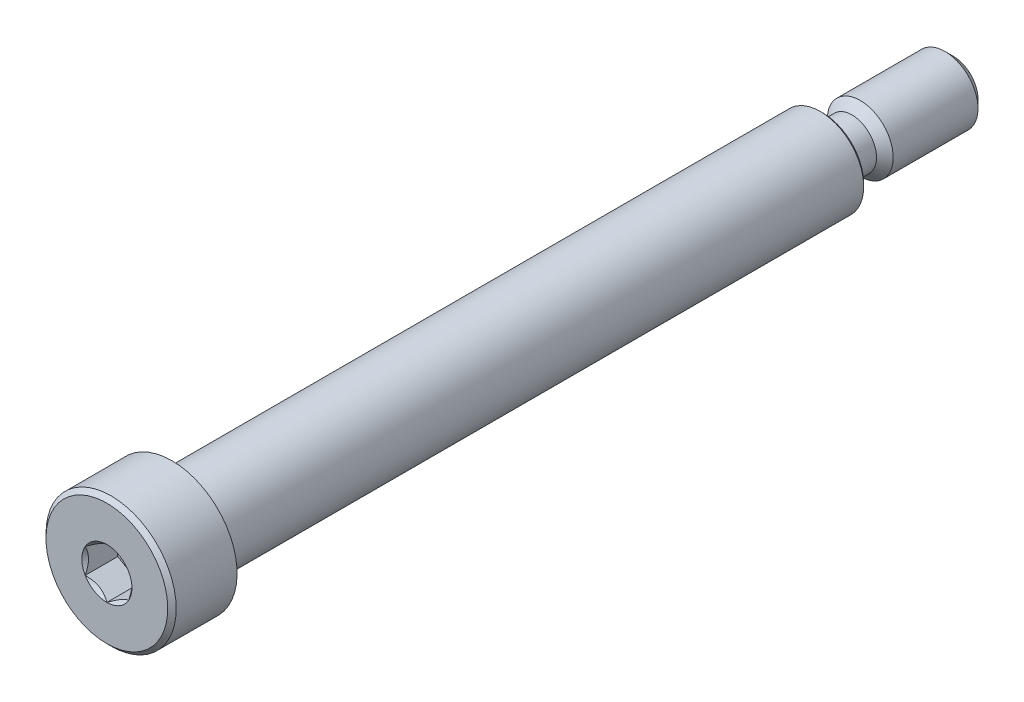
SolidWorks part; units mm, degrees
ref_plane "Front" through (0, 0, 0) normal (0, 0, 1) x (1, 0, 0)
ref_plane "Top" through (0, 0, 0) normal (0, 1, 0) x (1, 0, 0)
ref_plane "Right" through (0, 0, 0) normal (1, 0, 0) x (0, 0, -1)
sketch "Sketch1" plane through (0, 0, 0) normal (1, 0, 0) x (0, 0, -1)
  line L0 (0, 4.7625) -> (4.7625, 4.7625)
  line L1 (4.7625, 4.7625) -> (4.7625, 3.175)
  line L2 (4.7625, 3.175) -> (52.3875, 3.175)
  line L3 (52.3875, 3.175) -> (52.3875, 2.413)
  line L4 (52.3875, 2.413) -> (61.9125, 2.413)
  line L5 (61.9125, 2.413) -> (61.9125, 0)
  line L6 (61.9125, 0) -> (0, 0)
  line L7 (0, 0) -> (0, 4.7625)
  line L8 (0, 4.7625) -> (0, -4.7625) construction
  line L9 (61.9125, 2.413) -> (61.9125, -2.413) construction
  line L10 (52.3875, 3.175) -> (52.3875, -3.175) construction
  line L11 (61.9125, -2.413) -> (60.2347, -2.413) construction
  line L12 (28.575, 0) -> (28.575, 3.175) construction
  point P8 (60.325, -2.413)
  point P12 (52.3875, 0)
  point P17 (9.525, 3.175)
  point P18 (28.575, 0)
  point P19 (28.575, 3.175)
  point P20 (47.625, 3.175)
  point P21 (47.625, -3.175)
  point P22 (9.525, -3.175)
  dimension "Head Dia" = 9.525
  dimension "Head Ht" = 4.7625
  dimension "Thread Lg" = 9.525
  dimension "Thread Dia" = 4.826
  dimension "Shoulder Dia" = 6.35
  dimension "Shoulder Lg" = 47.625
  dimension "D1" = 1.5875
  dimension "D2" = 1.6778
  dimension "D3" = 23.8125
  dimension "D4" = 4.7625
revolve "Revolve1" add sketch "Sketch1" angle 360 mid plane about L6
ref_plane "Plane1" through (0, 0, -61.9125) normal (0, 0, 1) x (1, 0, 0)
sketch "Sketch3" [suppressed] plane through (0, 0, -61.9125) normal (0, 0, 1) x (1, 0, 0)
  circle A0 centre (0, 0) radius 2.413
sketch "Sketch5" plane through (0, 0, 0) normal (1, 0, 0) x (0, 0, -1)
  line L0 (52.3875, 3.175) -> (55.8673, 3.175)
  line L1 (55.8673, 3.175) -> (54.4957, 1.8034)
  line L2 (54.4957, 1.8034) -> (52.9971, 1.8034)
  line L3 (52.3875, 3.175) -> (52.3875, 2.413)
  line L5 (52.3875, 2.413) -> (61.9125, 2.413) construction
  line L6 (61.9125, 0) -> (54.4957, 0) construction
  line L7 (58.2041, 0) -> (58.2041, -2.413) construction
  arc A0 (52.3875, 2.413) -> (52.9971, 1.8034) centre (52.9971, 2.413) ccw
  dimension "D1" = 45
  dimension "CADB" = 2.1082
  dimension "CADA" = 3.6068
revolve "Cut-Revolve1" cut sketch "Sketch5" angle 360 mid plane about L6
chamfer "Chamfer1" distance 0.6032 angle 45 1 edges at (0, 2.413, -61.9125)
chamfer "Chamfer2" distance 0.3096 angle 45 1 edges at (0, 4.7625, 0)
chamfer "Chamfer3" distance 0.2032 angle 45 1 edges at (0, 3.175, -52.3875)
sketch "Sketch10" plane through (0, 0, 0) normal (1, 0, 0) x (0, 0, -1)
  line L0 (0.3096, 0) -> (4.4529, 0) construction
  line L1 (0.3096, -4.7625) -> (0.3096, 4.7625) construction
  line L3 (0.3096, 0) -> (0, 0) construction
  line L4 (4.4529, 0) -> (4.7625, 0) construction
  line L5 (4.7625, -4.7625) -> (4.7625, 4.7625) construction
  point P6 (2.3812, 0)
  dimension "D1" = 4.1434
ref_plane "Plane2" through (0, 0, -2.3812) normal (0, 0, 1) x (1, 0, 0)
sketch "Sketch11" plane through (0, 0, -2.3812) normal (0, 0, 1) x (1, 0, 0)
  line L0 (0, 4.5148) -> (0, 4.7625) construction
  line L1 (0, 4.5148) -> (0.143, 4.7625)
  line L2 (0, 4.5148) -> (-0.143, 4.7625)
  line L3 (-0.143, 4.7625) -> (0.143, 4.7625)
  line L4 (0, 0) -> (-0.143, 4.7625) construction
  line L5 (0.143, 4.7625) -> (0, 0) construction
  circle A1 centre (0, 0) radius 4.7625 construction
  circle A2 centre (0, 0) radius 4.5148 construction
  circle A3 centre (0, 0) radius 4.4529 construction
  point P3 (0, 0.0018)
  point P8 (2.3908, 0.7309)
  dimension "D1" = 0.2476
  dimension "D2" = 3.439
extrude "Cut-Extrude5" [suppressed] cut sketch "Sketch11" against normal mid plane 3.9362
pattern_circular "CirPattern1" [suppressed] count 99 over 360 of bodies 119
sketch "Sketch8" plane through (0, 0, 0) normal (0, 0, 1) x (1, 0, 0)
  line L1 (1.5875, 0.9165) -> (0, 1.8331)
  line L2 (0, 1.8331) -> (-1.5875, 0.9165)
  line L3 (-1.5875, 0.9165) -> (-1.5875, -0.9165)
  line L4 (-1.5875, -0.9165) -> (0, -1.8331)
  line L5 (0, -1.8331) -> (1.5875, -0.9165)
  line L6 (1.5875, -0.9165) -> (1.5875, 0.9165)
  circle A0 centre (0, 0) radius 1.5875 construction
  dimension "Hex" = 3.175
extrude "Cut-Extrude2" cut sketch "Sketch8" against normal blind 2.3813
sketch "Sketch9" plane through (0, 0, 0) normal (0, 0, 1) x (1, 0, 0)
  circle A0 centre (0, 0) radius 1.8331
extrude "Cut-Extrude4" cut sketch "Sketch9" against normal blind 2.3813 draft 45
sketch "Front Sketch" plane through (0, 0, 0) normal (0, 0, 1) x (1, 0, 0)
  line L0 (1.5875, -0.9165) -> (1.5875, 0.9165) construction
  line L1 (-1.5875, 0.9165) -> (-1.5875, -0.9165) construction
  circle A0 centre (0, 0) radius 4.7625 construction
  point P4 (-1.5875, 0)
  point P5 (1.5875, 0)
  point P6 (4.7625, 0)
  point P9 (-4.7625, 0)
ref_plane "Contact Plane 1" through (0, 0, -4.7625) normal (0, 0, -1) x (-1, 0, 0)
ref_axis "Center Axis 1" through (0, 0, -61.9125) along (0, 0, 1)
curve "Helix/Spiral1" [suppressed] pitch 1.0583 height 10.5833 turns 10
sketch "Sketch4" [suppressed] plane through (0, 0, 0) normal (1, 0, 0) x (0, 0, -1)
  line L0 (61.8464, 2.5276) -> (62.9047, 2.5276) construction
  line L1 (62.9047, 2.5276) -> (62.3755, 1.611) construction
  line L3 (62.3755, 1.611) -> (61.8464, 2.5276) construction
  line L4 (61.8794, 2.4703) -> (62.8716, 2.4703) construction
  line L5 (61.9125, 2.413) -> (62.8385, 2.413) construction
  line L6 (62.3094, 1.7256) -> (62.4417, 1.7256) construction
  line L7 (62.3755, 1.7256) -> (62.3755, 1.611) construction
  line L8 (62.3755, 2.5276) -> (62.3755, 2.413) construction
  line L9 (61.8794, 2.4703) -> (62.8716, 2.4703)
  line L10 (62.8716, 2.4703) -> (62.4417, 1.7256)
  line L11 (62.4417, 1.7256) -> (62.3094, 1.7256)
  line L12 (62.3094, 1.7256) -> (61.8794, 2.4703)
  point P14 (62.3755, 2.4703)
  point P15 (62.3755, 2.5276)
  dimension "D1" = 1.0583
  dimension "D2" = 0.1323
sweep "Cut-Sweep1" [suppressed] cut profiles "Sketch4" path "Helix/Spiral1"
sketch "Sketch12" [suppressed] plane through (0, 0, 0) normal (1, 0, 0) x (0, 0, -1)
  line L1 (52.3875, 2.9718) -> (52.1843, 3.175)
  line L2 (52.1843, 3.175) -> (4.7625, 3.175)
  line L3 (4.7625, 3.175) -> (4.7625, 0)
  line L4 (4.7625, -4.7625) -> (4.7625, 4.7625) construction
  line L5 (4.7625, 0) -> (52.3875, 0)
  line L6 (52.3875, 2.9718) -> (52.3875, 2.413)
  line L7 (54.4957, 1.8034) -> (52.9971, 1.8034) construction
  line L8 (54.4957, 1.8034) -> (52.9971, 1.8034)
  line L9 (54.4957, 1.8034) -> (54.4957, 0)
  line L10 (54.4957, 0) -> (52.3875, 0)
  arc A0 (52.3875, 2.413) -> (52.9971, 1.8034) centre (52.9971, 2.413) ccw construction
  arc A1 (52.3875, 2.413) -> (52.9971, 1.8034) centre (52.9971, 2.413) ccw
revolve "Revolve2" [suppressed] add sketch "Sketch12" angle 360 about L5
equation "\"D3@Helix/Spiral1\" = \"Thread Lg@Sketch1\" + \"D4@Helix/Spiral1\""
equation "\"D1@Chamfer1\" = \"Thread Dia@Sketch1\" * .125"
equation "\"D1@Cut-Extrude2\"= \"Head Ht@Sketch1\" * .5"
equation "\"D1@Cut-Extrude4\" = \"D1@Cut-Extrude2\""
equation "\"D1@Chamfer2\" = \"Head Dia@Sketch1\" * .0325"
equation "\"D1@Sketch1\"=\"D4@Helix/Spiral1\"*1.5"
equation "\"D1@Sketch11\"=\"D1@Chamfer2\"*.8"
equation "\"D1@Cut-Extrude5\"=\"D1@Sketch10\"*.95"
equation "\"D1@CirPattern1\"=(360/\"D2@Sketch11\")-6"
equation "\"D3@Sketch1\"=\"Shoulder Lg@Sketch1\"/2"
equation "\"D4@Sketch1\"=\"D3@Sketch1\"*.2"
equation "\"D1@Sketch4\"=\"D4@Helix/Spiral1\""
equation "\"D2@Sketch4\"=\"D1@Sketch4\"/8"
